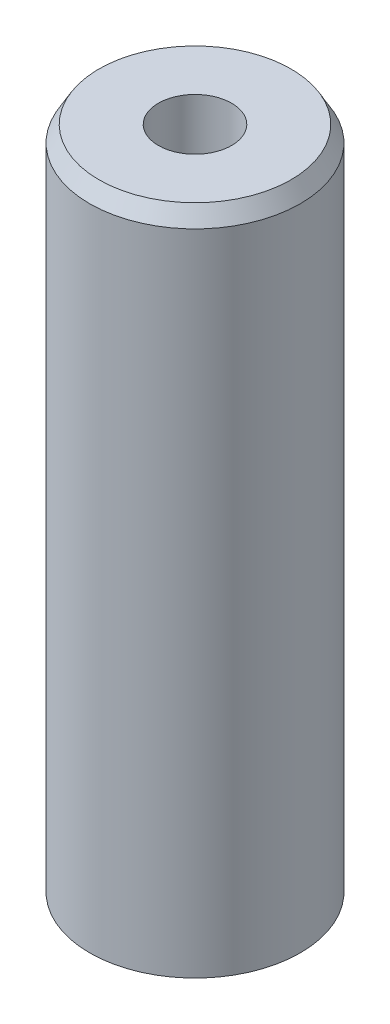
SolidWorks part; units mm, degrees
ref_plane "Front Plane" through (0, 0, 0) normal (0, 0, 1) x (1, 0, 0)
ref_plane "Top Plane" through (0, 0, 0) normal (0, 1, 0) x (1, 0, 0)
ref_plane "Right Plane" through (0, 0, 0) normal (1, 0, 0) x (0, 0, -1)
sketch "Sketch1" plane through (0, 0, 0) normal (0, 1, 0) x (1, 0, 0)
  circle A0 centre (0, 0) radius 7.5
  dimension "SHAFT_OD" = 15
extrude "Boss-Extrude1" add sketch "Sketch1" along normal blind 48.0076
sketch "Sketch2" plane through (0, 0, 0) normal (0, 1, 0) x (1, 0, 0)
  circle A0 centre (0, 0) radius 2.6099
  dimension "BORE_D" = 5.2198
extrude "Cut-Extrude1" cut sketch "Sketch2" along normal through all
chamfer "Chamfer1" distance 1.146 angle 30 2 edges at (0, 48.0076, 7.5) (0, 0, 7.5) first distance on face at (0, 48.0076, 7.5) first distance on face at (0, 0, 2.6099)
